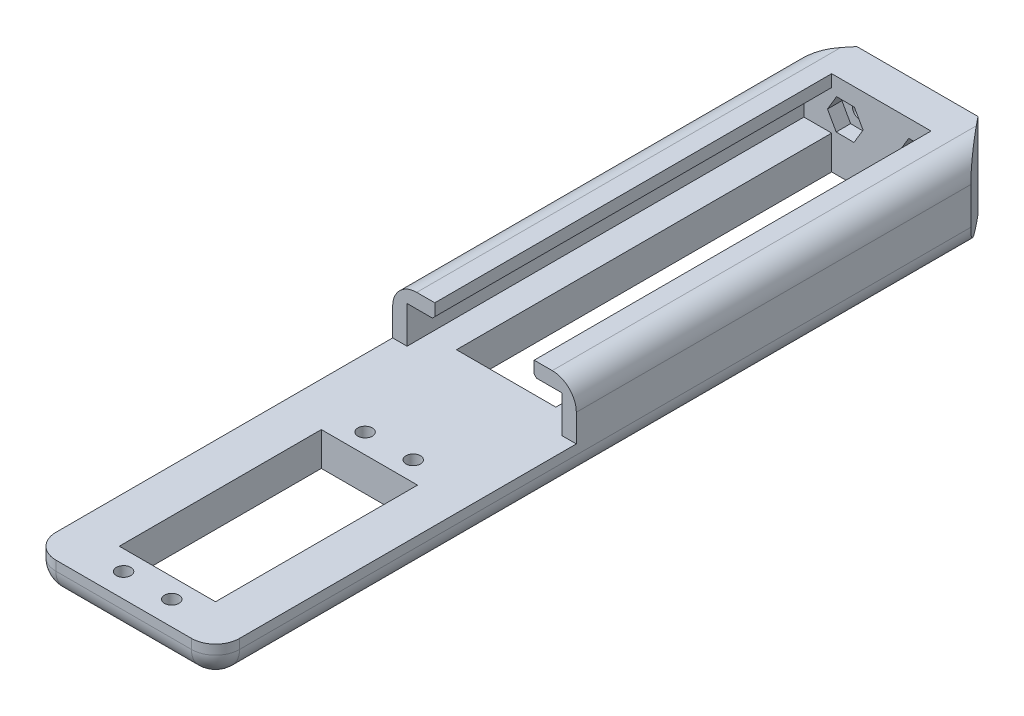
SolidWorks part; units mm, degrees
ref_plane "Front Plane" through (0, 0, 0) normal (0, 0, 1) x (1, 0, 0)
ref_plane "Top Plane" through (0, 0, 0) normal (0, 1, 0) x (1, 0, 0)
ref_plane "Right Plane" through (0, 0, 0) normal (1, 0, 0) x (0, 0, -1)
sketch "Sketch1" plane through (0, 0, 0) normal (0, 0, 1) x (1, 0, 0)
  line L0 (-69.7691, 23.4512) -> (-75.5286, 23.4512)
  line L1 (-75.5286, 23.4512) -> (-75.5286, 15.7512)
  line L2 (-75.5286, 15.7512) -> (-69.7691, 15.7512)
  line L3 (-69.7691, 15.7512) -> (-69.7691, 8.7512)
  line L4 (-69.7691, 8.7512) -> (-78.5286, 8.7512)
  line L5 (-78.5286, 8.7512) -> (-78.5286, 26.4512)
  line L6 (-78.5286, 26.4512) -> (-69.7691, 26.4512)
  line L7 (-69.7691, 26.4512) -> (-69.7691, 23.4512)
  line L8 (-49.1122, 23.4512) -> (-49.1122, 26.4512)
  line L9 (-49.1122, 26.4512) -> (-40.3527, 26.4512)
  line L10 (-40.3527, 26.4512) -> (-40.3527, 8.7512)
  line L11 (-40.3527, 8.7512) -> (-49.1122, 8.7512)
  line L12 (-49.1122, 8.7512) -> (-49.1122, 15.7512)
  line L13 (-49.1122, 15.7512) -> (-43.3527, 15.7512)
  line L14 (-43.3527, 15.7512) -> (-43.3527, 23.4512)
  line L15 (-43.3527, 23.4512) -> (-49.1122, 23.4512)
  dimension "D1" = 17.7
  dimension "D2" = 5.7594
  dimension "D3" = 20.657
  dimension "D4" = 7.7
  dimension "D8" = 3
  dimension "D9" = 3
extrude "Boss-Extrude1" add sketch "Sketch1" along normal blind 55 and the other way blind 35
sketch "Sketch2" plane through (0, 26.4512, 0) normal (0, 1, 0) x (1, 0, 0)
  line L0 (-40.3527, 35) -> (-40.3527, -55) construction
  line L6 (-78.5286, 35) -> (-40.3527, 35)
  line L7 (-78.5286, 35) -> (-78.5286, 27.5)
  line L8 (-78.5286, 27.5) -> (-40.3527, 27.5)
  line L9 (-40.3527, 35) -> (-40.3527, 27.5)
  dimension "D1" = 7.5
extrude "Boss-Extrude2" add sketch "Sketch2" against normal up to vertex (3 mm away) up to point (-69.7691, 23.4512, -35)
sketch "Sketch3" plane through (0, 8.7512, 0) normal (0, -1, 0) x (1, 0, 0)
  line L0 (-40.3527, -35) -> (-40.3527, 55) construction
  line L1 (-78.5286, 55) -> (-40.3527, 55)
  line L2 (-78.5286, 55) -> (-78.5286, 47.5)
  line L3 (-78.5286, 47.5) -> (-40.3527, 47.5)
  line L4 (-40.3527, 55) -> (-40.3527, 47.5)
  line L6 (-78.5286, -35) -> (-40.3527, -35)
  line L7 (-78.5286, -35) -> (-78.5286, -27.5)
  line L8 (-78.5286, -27.5) -> (-40.3527, -27.5)
  line L9 (-40.3527, -35) -> (-40.3527, -27.5)
  line L10 (-69.7691, -27.5) -> (-49.1122, -27.5) construction
extrude "Boss-Extrude3" add sketch "Sketch3" against normal up to vertex (7 mm away) up to point (-69.7691, 15.7512, 55)
ref_plane "MidSlide" through (0, 19.6012, 0) normal (0, 1, 0) x (1, 0, 0)
ref_plane "Plane2" through (-59.4407, 0, 0) normal (1, 0, 0) x (0, 0, -1)
sketch "Sketch11" plane through (0, 15.7512, 0) normal (0, 1, 0) x (1, 0, 0)
  line L0 (-49.4407, -99.9121) -> (-40.3527, -99.9121) construction
  line L1 (-40.3527, -130) -> (-78.5286, -130)
  line L2 (-40.3527, -130) -> (-40.3527, -55)
  line L3 (-40.3527, -55) -> (-78.5286, -55)
  line L4 (-78.5286, -130) -> (-78.5286, -55)
  line L5 (-49.4407, -120.9121) -> (-69.4407, -120.9121)
  line L6 (-49.4407, -120.9121) -> (-49.4407, -78.9121)
  line L7 (-49.4407, -78.9121) -> (-69.4407, -78.9121)
  line L8 (-69.4407, -120.9121) -> (-69.4407, -78.9121)
  line L9 (-69.4407, -99.9121) -> (-78.5286, -99.9121) construction
  line L10 (-59.4407, -120.9121) -> (-59.4407, -130) construction
  line L11 (-49.4407, -78.9121) -> (-49.4407, -74.8121) construction
  line L12 (-54.4407, -74.8121) -> (-54.4407, -78.9121) construction
  line L13 (-54.4407, -125.0121) -> (-54.4407, -120.9121) construction
  line L14 (-49.4407, -74.8121) -> (-54.4407, -74.8121) construction
  line L15 (-54.4407, -74.8121) -> (-64.4407, -74.8121) construction
  line L16 (-64.4407, -74.8121) -> (-69.4407, -74.8121) construction
  line L17 (-69.4407, -74.8121) -> (-69.4407, -78.9121) construction
  line L19 (-59.4407, -9.735) -> (-59.4407, 9.735) construction
  line L20 (-43.3527, -55) -> (-75.5286, -55) construction
  line L21 (-78.5286, 35) -> (-78.5286, -55) construction
  circle A0 centre (-54.4407, -125.0121) radius 1.5
  circle A1 centre (-64.4407, -125.0121) radius 1.5
  circle A2 centre (-54.4407, -74.8121) radius 1.5
  circle A3 centre (-64.4407, -74.8121) radius 1.5
  point P28 (-59.4407, -55)
  dimension "D5" = 10
  dimension "D4" = 3
  dimension "D1" = 75
  dimension "D2" = 20
  dimension "D3" = 42
  dimension "D6" = 4.1
extrude "Boss-Extrude7" add sketch "Sketch11" against normal blind 7
sketch "Sketch6" plane through (0, 0, -35) normal (0, 0, -1) x (-1, 0, 0)
  line L1 (43.3527, 23.4512) -> (75.5286, 23.4512)
  line L2 (43.3527, 23.4512) -> (43.3527, 15.7512)
  line L3 (43.3527, 15.7512) -> (75.5286, 15.7512)
  line L4 (75.5286, 23.4512) -> (75.5286, 15.7512)
  line L6 (43.3527, 23.4512) -> (43.3527, 15.7512) construction
  line L7 (43.3527, 15.7512) -> (75.5286, 15.7512) construction
  line L8 (75.5286, 23.4512) -> (43.3527, 23.4512) construction
  line L9 (75.5286, 15.7512) -> (75.5286, 23.4512) construction
sketch "Sketch7" plane through (0, 0, -35) normal (0, 0, -1) x (-1, 0, 0)
  line L0 (78.5286, 8.7512) -> (78.5286, 26.4512) construction
  line L1 (78.5286, 26.4512) -> (40.3527, 26.4512) construction
  line L2 (40.3527, 8.7512) -> (40.3527, 26.4512) construction
  line L3 (40.3527, 26.4512) -> (78.5286, 26.4512) construction
  line L4 (40.3527, 26.4512) -> (40.3527, 8.7512) construction
  line L5 (40.3527, 8.7512) -> (78.5286, 8.7512) construction
  line L6 (75.5286, 15.7512) -> (75.5286, 23.4512) construction
  line L7 (75.5286, 19.6012) -> (66.9407, 19.6012) construction
  line L8 (75.5286, 23.4512) -> (43.3527, 23.4512) construction
  line L9 (51.9407, 19.6012) -> (43.3527, 19.6012) construction
  line L10 (43.3527, 23.4512) -> (43.3527, 15.7512) construction
  circle A0 centre (66.9407, 19.6012) radius 1.5
  circle A1 centre (51.9407, 19.6012) radius 1.5
  dimension "D2" = 3
  dimension "D1" = 15
sketch "Sketch9" plane through (0, 26.4512, 0) normal (0, 1, 0) x (1, 0, 0)
  line L0 (-72.0286, 35) -> (-78.5286, 35)
  line L1 (-40.3527, 35) -> (-78.5286, 35) construction
  line L2 (-78.5286, 35) -> (-78.5286, 27)
  line L3 (-78.5286, 35) -> (-78.5286, -55) construction
  line L4 (-78.5286, 27) -> (-72.0286, 35)
  line L5 (-46.8527, 35) -> (-40.3527, 35)
  line L6 (-40.3527, 35) -> (-40.3527, 27)
  line L7 (-40.3527, -55) -> (-40.3527, 35) construction
  line L8 (-40.3527, 27) -> (-46.8527, 35)
  dimension "D1" = 8
  dimension "D2" = 6.5
ref_plane "Plane3" through (-40.3527, 26.4512, -35) normal (0, 0, -1) x (-1, 0, 0)
extrude "Boss-Extrude8" add sketch "Sketch6" against normal blind 7.5
extrude "Cut-Extrude1" cut sketch "Sketch9" against normal blind 18
extrude "Cut-Extrude2" cut sketch "Sketch7" against normal blind 10
sketch "Sketch14" plane through (0, 0, -27.5) normal (0, 0, 1) x (1, 0, 0)
  line L1 (-65.0515, 22.7829) -> (-68.7515, 22.8281)
  line L2 (-68.7515, 22.8281) -> (-70.6407, 19.6464)
  line L3 (-70.6407, 19.6464) -> (-68.8298, 16.4195)
  line L4 (-68.8298, 16.4195) -> (-65.1298, 16.3743)
  line L5 (-65.1298, 16.3743) -> (-63.2407, 19.556)
  line L6 (-63.2407, 19.556) -> (-65.0515, 22.7829)
  line L7 (-55.6407, 19.6464) -> (-53.8298, 16.4195)
  line L8 (-53.8298, 16.4195) -> (-50.1298, 16.3743)
  line L9 (-50.1298, 16.3743) -> (-48.2407, 19.556)
  line L10 (-48.2407, 19.556) -> (-50.0515, 22.7829)
  line L11 (-50.0515, 22.7829) -> (-53.7515, 22.8281)
  line L12 (-53.7515, 22.8281) -> (-55.6407, 19.6464)
  circle A0 centre (-66.9407, 19.6012) radius 3.2045 construction
  circle A1 centre (-51.9407, 19.6012) radius 3.2045 construction
  dimension "D1" = 3.7
extrude "Cut-Extrude3" cut sketch "Sketch14" against normal blind 3
chamfer "Chamfer1" distance 0.5 angle 45 2 edges at (-69.7691, 23.4512, 13.75) (-49.1122, 23.4512, 13.75)
chamfer "Chamfer2" distance 10 angle 45 1 edges at (-59.4407, 8.7512, 47.5)
fillet "Fillet38" radius 5 4 edges at (-40.3527, 8.7512, 51.5) (-78.5286, 26.4512, 14) (-40.3527, 26.4512, 14) (-78.5286, 8.7512, 51.5)
fillet "Fillet39" radius 5 5 edges at (-77.0641, 10.2156, 130) (-59.4407, 8.7512, 130) (-41.8172, 10.2156, 130) (-78.5286, 14.7512, 130) (-40.3527, 14.7512, 130)
